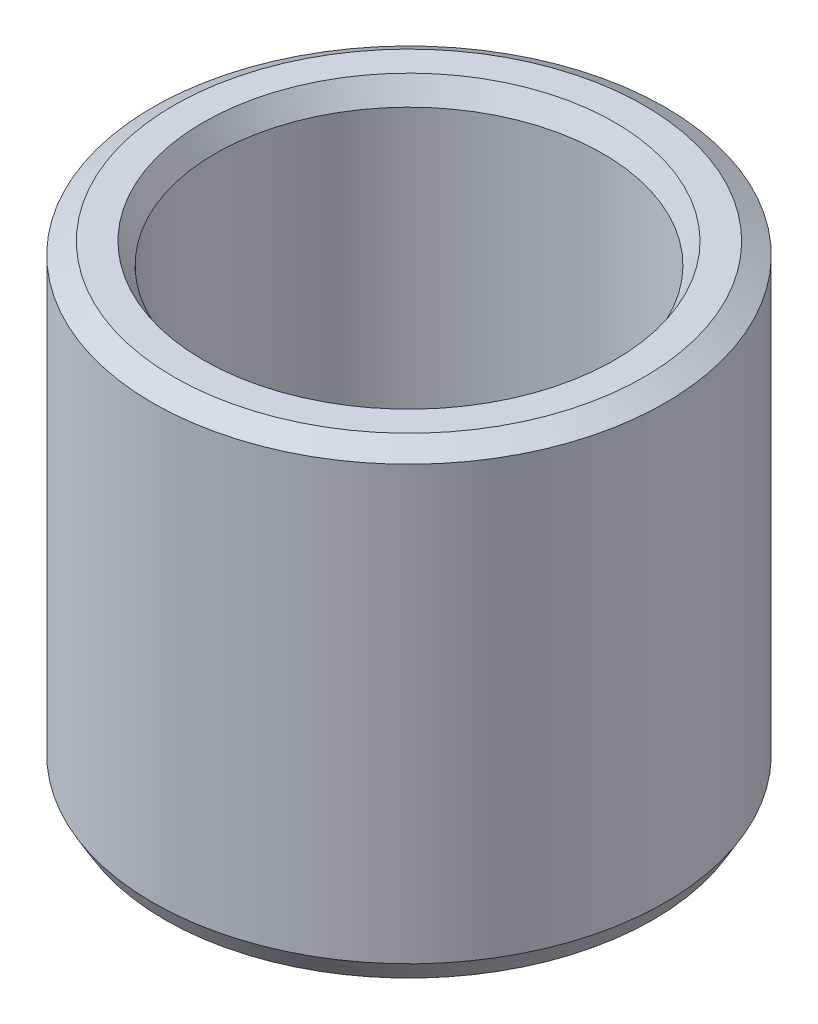
SolidWorks part; units mm, degrees
ref_plane "Front Plane" through (0, 0, 0) normal (0, 0, 1) x (1, 0, 0)
ref_plane "Top Plane" through (0, 0, 0) normal (0, 1, 0) x (1, 0, 0)
ref_plane "Right Plane" through (0, 0, 0) normal (1, 0, 0) x (0, 0, -1)
sketch "Sketch1" plane through (0, 0, 0) normal (0, 1, 0) x (1, 0, 0)
  circle A0 centre (0, 0) radius 22.5
  dimension "SLEEVE_OD" = 45
extrude "Boss-Extrude1" add sketch "Sketch1" along normal blind 40.8985
sketch "Sketch2" plane through (0, 0, 0) normal (0, 1, 0) x (1, 0, 0)
  circle A0 centre (0, 0) radius 17.0155
  dimension "BORE_D" = 34.0309
extrude "Cut-Extrude1" cut sketch "Sketch2" along normal through all
chamfer "Chamfer1" distance 1.0612 angle 60 4 edges at (0, 40.8985, 17.0155) (0, 0, 17.0155) (0, 0, 22.5) (0, 40.8985, 22.5) first distance on face at (0, 40.8985, 17.0155) first distance on face at (0, 0, 17.0155) first distance on face at (0, 40.8985, 22.5)
